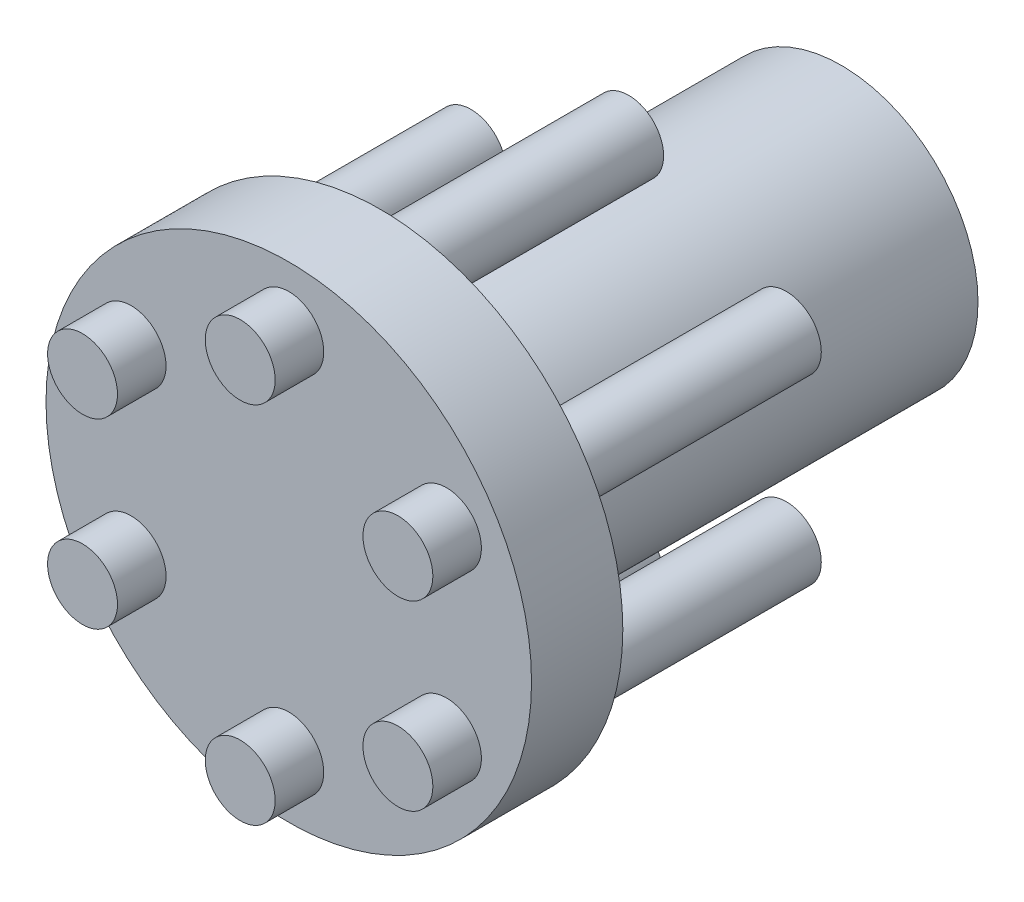
SolidWorks part; units mm, degrees
ref_plane "Front Plane" through (0, 0, 0) normal (0, 0, 1) x (1, 0, 0)
ref_plane "Top Plane" through (0, 0, 0) normal (0, 1, 0) x (1, 0, 0)
ref_plane "Right Plane" through (0, 0, 0) normal (1, 0, 0) x (0, 0, -1)
sketch "Sketch1" plane through (0, 0, 0) normal (0, 0, 1) x (1, 0, 0)
  circle A0 centre (0, 0) radius 12.7
  dimension "D1" = 25.4
extrude "Boss-Extrude1" add sketch "Sketch1" along normal blind 4.7752
sketch "Sketch2" plane through (0, 0, 0) normal (0, 0, -1) x (-1, 0, 0)
  circle A0 centre (0, 0) radius 7.1501
  dimension "D1" = 14.3002
extrude "Boss-Extrude2" add sketch "Sketch2" along normal blind 24.13
sketch "Sketch3" plane through (0, 0, 4.7752) normal (0, 0, 1) x (1, 0, 0)
  circle A0 centre (0, 0) radius 9.525 construction
  circle A1 centre (0, 9.525) radius 1.8288
  circle A2 centre (8.2489, 4.7625) radius 1.8288
  circle A3 centre (8.2489, -4.7625) radius 1.8288
  circle A4 centre (0, -9.525) radius 1.8288
  circle A5 centre (-8.2489, -4.7625) radius 1.8288
  circle A6 centre (-8.2489, 4.7625) radius 1.8288
  point P18 (0, 0)
  dimension "D1" = 19.05
  dimension "D2" = 3.6576
  dimension "D3" = 6
extrude "Boss-Extrude3" add sketch "Sketch3" along normal blind 2.54 and the other way blind 17.78
sketch "Sketch4" plane through (0, 0, 4.7752) normal (0, 0, 1) x (1, 0, 0)
  line L0 (0, 12.7) -> (0, -12.7) construction
  circle A0 centre (0, 0) radius 12.7 construction
